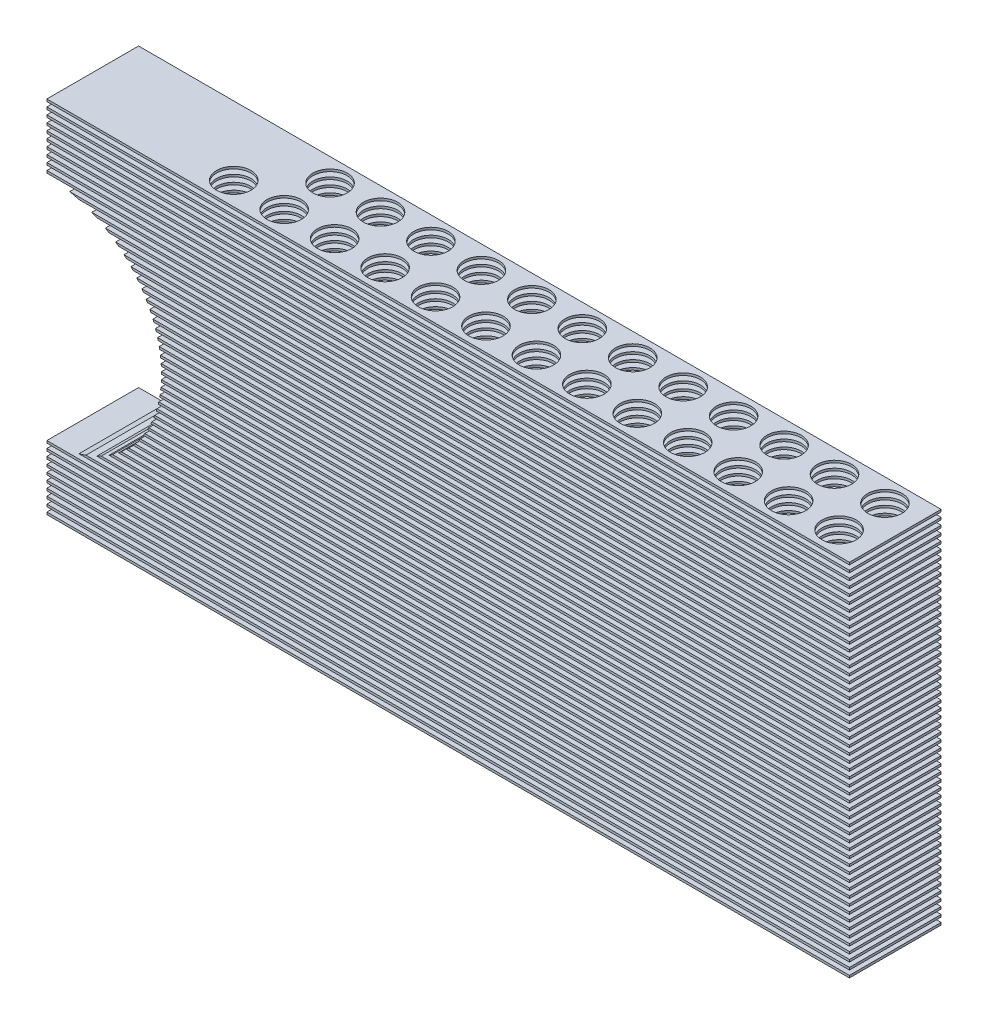
SolidWorks part; units mm, degrees
ref_plane "Alzado" through (0, 0, 0) normal (0, 0, 1) x (1, 0, 0)
ref_plane "Planta" through (0, 0, 0) normal (0, 1, 0) x (1, 0, 0)
ref_plane "Vista lateral" through (0, 0, 0) normal (1, 0, 0) x (0, 0, -1)
sketch "Croquis2" plane through (0, 0, 0) normal (0, 0, 1) x (1, 0, 0)
  line L0 (-175, 74) -> (-175, 75)
  line L2 (-175, 77) -> (-175, 78)
  line L4 (175, 77) -> (175, 78)
  line L5 (-175, 75) -> (175, 75)
  line L6 (175, 74) -> (-175, 74)
  line L7 (-175, 78) -> (175, 78)
  line L9 (175, 77) -> (-175, 77)
  line L11 (175, 74) -> (175, 75)
  line L12 (-175, 71) -> (-175, 72)
  line L13 (-175, 72) -> (175, 72)
  line L14 (175, 71) -> (-175, 71)
  line L15 (175, 71) -> (175, 72)
  line L16 (-175, 68) -> (-175, 69)
  line L17 (-175, 69) -> (175, 69)
  line L18 (175, 68) -> (-175, 68)
  line L19 (175, 68) -> (175, 69)
  line L20 (-175, 65) -> (-175, 66)
  line L21 (-175, 66) -> (175, 66)
  line L22 (175, 65) -> (-175, 65)
  line L23 (175, 65) -> (175, 66)
  line L24 (-175, 62) -> (-175, 63)
  line L25 (-175, 63) -> (175, 63)
  line L26 (175, 62) -> (-175, 62)
  line L27 (175, 62) -> (175, 63)
  line L28 (-175, 59) -> (-175, 60)
  line L29 (-175, 60) -> (175, 60)
  line L30 (175, 59) -> (-175, 59)
  line L31 (175, 59) -> (175, 60)
  line L32 (-175, 56) -> (-175, 57)
  line L33 (-175, 57) -> (175, 57)
  line L34 (175, 56) -> (-175, 56)
  line L35 (175, 56) -> (175, 57)
  line L36 (-175, 53) -> (-175, 54)
  line L37 (-175, 54) -> (175, 54)
  line L38 (175, 53) -> (-175, 53)
  line L39 (175, 53) -> (175, 54)
  line L40 (-175, 50) -> (-175, 51)
  line L41 (-175, 51) -> (175, 51)
  line L42 (175, 50) -> (-175, 50)
  line L43 (175, 50) -> (175, 51)
  line L45 (-165.0501, 48) -> (175, 48)
  line L46 (175, 47) -> (-161, 47)
  line L47 (175, 47) -> (175, 48)
  line L49 (-155.4041, 45) -> (175, 45)
  line L50 (175, 44) -> (-153.2055, 44)
  line L51 (175, 44) -> (175, 45)
  line L53 (-149.4853, 42) -> (175, 42)
  line L54 (175, 41) -> (-147.8707, 41)
  line L55 (175, 41) -> (175, 42)
  line L57 (-145, 39) -> (175, 39)
  line L58 (175, 38) -> (-143.711, 38)
  line L59 (175, 38) -> (175, 39)
  line L61 (-141.3697, 36) -> (175, 36)
  line L62 (175, 35) -> (-140.3013, 35)
  line L63 (175, 35) -> (175, 36)
  line L65 (-138.3394, 33) -> (175, 33)
  line L66 (175, 32) -> (-137.4367, 32)
  line L67 (175, 32) -> (175, 33)
  line L69 (-135.7699, 30) -> (175, 30)
  line L70 (175, 29) -> (-135, 29)
  line L71 (175, 29) -> (175, 30)
  line L73 (-133.5754, 27) -> (175, 27)
  line L74 (175, 26) -> (-132.9167, 26)
  line L75 (175, 26) -> (175, 27)
  line L77 (-131.6987, 24) -> (175, 24)
  line L78 (175, 23) -> (-131.1366, 23)
  line L79 (175, 23) -> (175, 24)
  line L81 (-130.1001, 21) -> (175, 21)
  line L82 (175, 20) -> (-129.6238, 20)
  line L83 (175, 20) -> (175, 21)
  line L85 (-128.7507, 18) -> (175, 18)
  line L86 (175, 17) -> (-128.3524, 17)
  line L87 (175, 17) -> (175, 18)
  line L89 (-127.6291, 15) -> (175, 15)
  line L90 (175, 14) -> (-127.303, 14)
  line L91 (175, 14) -> (175, 15)
  line L93 (-126.7196, 12) -> (175, 12)
  line L94 (175, 11) -> (-126.4614, 11)
  line L95 (175, 11) -> (175, 12)
  line L97 (-126.0102, 9) -> (175, 9)
  line L98 (175, 8) -> (-125.8167, 8)
  line L99 (175, 8) -> (175, 9)
  line L101 (-125.4924, 6) -> (175, 6)
  line L102 (175, 5) -> (-125.3613, 5)
  line L103 (175, 5) -> (175, 6)
  line L105 (-125.1603, 3) -> (175, 3)
  line L106 (175, 2) -> (-125.0901, 2)
  line L107 (175, 2) -> (175, 3)
  line L109 (-125.01, 0) -> (175, 0)
  line L110 (175, -1) -> (-125, -1)
  line L111 (175, -1) -> (175, 0)
  line L113 (-125.04, -3) -> (175, -3)
  line L114 (175, -4) -> (-125.0901, -4)
  line L115 (175, -4) -> (175, -3)
  line L117 (-125.2506, -6) -> (175, -6)
  line L118 (175, -7) -> (-125.3613, -7)
  line L119 (175, -7) -> (175, -6)
  line L121 (-125.6441, -9) -> (175, -9)
  line L122 (175, -10) -> (-125.8167, -10)
  line L123 (175, -10) -> (175, -9)
  line L125 (-126.225, -12) -> (175, -12)
  line L126 (175, -13) -> (-126.4614, -13)
  line L127 (175, -13) -> (175, -12)
  line L129 (-127, -15) -> (175, -15)
  line L130 (175, -16) -> (-127.303, -16)
  line L131 (175, -16) -> (175, -15)
  line L133 (-127.9787, -18) -> (175, -18)
  line L134 (175, -19) -> (-128.3524, -19)
  line L135 (175, -19) -> (175, -18)
  line L137 (-129.1742, -21) -> (175, -21)
  line L138 (175, -22) -> (-129.6238, -22)
  line L139 (175, -22) -> (175, -21)
  line L141 (-130.6041, -24) -> (175, -24)
  line L142 (175, -25) -> (-131.1366, -25)
  line L143 (175, -25) -> (175, -24)
  line L145 (-132.2917, -27) -> (175, -27)
  line L146 (175, -28) -> (-132.9167, -28)
  line L147 (175, -28) -> (175, -27)
  line L149 (-134.2692, -30) -> (175, -30)
  line L150 (175, -31) -> (-135, -31)
  line L151 (175, -31) -> (175, -30)
  line L153 (-136.5813, -33) -> (175, -33)
  line L154 (175, -34) -> (-137.4367, -34)
  line L155 (175, -34) -> (175, -33)
  line L157 (-139.2929, -36) -> (175, -36)
  line L158 (175, -37) -> (-140.3013, -37)
  line L159 (175, -37) -> (175, -36)
  line L161 (-142.5038, -39) -> (175, -39)
  line L162 (175, -40) -> (-143.711, -40)
  line L163 (175, -40) -> (175, -39)
  line L165 (-146.3818, -42) -> (175, -42)
  line L166 (175, -43) -> (-147.8707, -43)
  line L167 (175, -43) -> (175, -42)
  line L169 (-151.2513, -45) -> (175, -45)
  line L170 (175, -46) -> (-153.2055, -46)
  line L171 (175, -46) -> (175, -45)
  line L173 (-157.9413, -48) -> (175, -48)
  line L174 (175, -49) -> (-161, -49)
  line L175 (175, -49) -> (175, -48)
  line L176 (-175, -52) -> (-175, -51)
  line L177 (-175, -51) -> (175, -51)
  line L178 (175, -52) -> (-175, -52)
  line L179 (175, -52) -> (175, -51)
  line L180 (-175, -55) -> (-175, -54)
  line L181 (-175, -54) -> (175, -54)
  line L182 (175, -55) -> (-175, -55)
  line L183 (175, -55) -> (175, -54)
  line L184 (-175, -58) -> (-175, -57)
  line L185 (-175, -57) -> (175, -57)
  line L186 (175, -58) -> (-175, -58)
  line L187 (175, -58) -> (175, -57)
  line L188 (-175, -61) -> (-175, -60)
  line L189 (-175, -60) -> (175, -60)
  line L190 (175, -61) -> (-175, -61)
  line L191 (175, -61) -> (175, -60)
  line L192 (-175, -64) -> (-175, -63)
  line L193 (-175, -63) -> (175, -63)
  line L194 (175, -64) -> (-175, -64)
  line L195 (175, -64) -> (175, -63)
  line L196 (-175, -67) -> (-175, -66)
  line L197 (-175, -66) -> (175, -66)
  line L198 (175, -67) -> (-175, -67)
  line L199 (175, -67) -> (175, -66)
  line L200 (-175, -70) -> (-175, -69)
  line L201 (-175, -69) -> (175, -69)
  line L202 (175, -70) -> (-175, -70)
  line L203 (175, -70) -> (175, -69)
  line L204 (-175, -73) -> (-175, -72)
  line L205 (-175, -72) -> (175, -72)
  line L206 (175, -73) -> (-175, -73)
  line L207 (175, -73) -> (175, -72)
  line L208 (-175, -76) -> (-175, -75)
  line L209 (-175, -75) -> (175, -75)
  line L210 (175, -76) -> (-175, -76)
  line L211 (175, -76) -> (175, -75)
  line L212 (-175, -79) -> (-175, -78)
  line L213 (-175, -78) -> (175, -78)
  line L214 (175, -79) -> (-175, -79)
  line L215 (175, -79) -> (175, -78)
  line L221 (-175, 29) -> (-175, 30) [skipped]
  line L222 (-175, -43) -> (-175, -42) [skipped]
  line L223 (-175, 47) -> (-175, 48) [skipped]
  line L224 (-175, 44) -> (-175, 45) [skipped]
  line L225 (-175, 41) -> (-175, 42) [skipped]
  line L226 (-175, 38) -> (-175, 39) [skipped]
  line L227 (-175, 35) -> (-175, 36) [skipped]
  line L228 (-175, 32) -> (-175, 33) [skipped]
  line L229 (-175, 26) -> (-175, 27) [skipped]
  line L230 (-175, 23) -> (-175, 24) [skipped]
  line L231 (-175, 20) -> (-175, 21) [skipped]
  line L232 (-175, -19) -> (-175, -18) [skipped]
  line L233 (-175, -16) -> (-175, -15) [skipped]
  line L234 (-175, -13) -> (-175, -12) [skipped]
  line L235 (-175, -10) -> (-175, -9) [skipped]
  line L236 (-175, -7) -> (-175, -6) [skipped]
  line L237 (-175, -4) -> (-175, -3) [skipped]
  line L238 (-175, -1) -> (-175, 0) [skipped]
  line L239 (-175, 2) -> (-175, 3) [skipped]
  line L240 (-175, 17) -> (-175, 18) [skipped]
  line L241 (-175, 14) -> (-175, 15) [skipped]
  line L242 (-175, 11) -> (-175, 12) [skipped]
  line L243 (-175, 8) -> (-175, 9) [skipped]
  line L244 (-175, 5) -> (-175, 6) [skipped]
  line L245 (-175, -49) -> (-175, -48) [skipped]
  line L246 (-175, -46) -> (-175, -45) [skipped]
  line L247 (-175, -40) -> (-175, -39) [skipped]
  line L248 (-175, -22) -> (-175, -21) [skipped]
  line L249 (-175, -25) -> (-175, -24) [skipped]
  line L250 (-175, -28) -> (-175, -27) [skipped]
  line L251 (-175, -31) -> (-175, -30) [skipped]
  line L252 (-175, -34) -> (-175, -33) [skipped]
  line L253 (-175, -37) -> (-175, -36) [skipped]
  arc A0 (-161, -49) -> (-157.9413, -48) centre (-175, -1) ccw
  arc A1 (-153.2055, -46) -> (-151.2513, -45) centre (-175, -1) ccw
  arc A2 (-147.8707, -43) -> (-146.3818, -42) centre (-175, -1) ccw
  arc A3 (-143.711, -40) -> (-142.5038, -39) centre (-175, -1) ccw
  arc A4 (-140.3013, -37) -> (-139.2929, -36) centre (-175, -1) ccw
  arc A5 (-137.4367, -34) -> (-136.5813, -33) centre (-175, -1) ccw
  arc A6 (-128.3524, -19) -> (-127.9787, -18) centre (-175, -1) ccw
  arc A7 (-129.6238, -22) -> (-129.1742, -21) centre (-175, -1) ccw
  arc A8 (-131.1366, -25) -> (-130.6041, -24) centre (-175, -1) ccw
  arc A9 (-135, -31) -> (-134.2692, -30) centre (-175, -1) ccw
  arc A10 (-132.9167, -28) -> (-132.2917, -27) centre (-175, -1) ccw
  arc A11 (-127.303, -16) -> (-127, -15) centre (-175, -1) ccw
  arc A12 (-126.4614, -13) -> (-126.225, -12) centre (-175, -1) ccw
  arc A13 (-125.8167, -10) -> (-125.6441, -9) centre (-175, -1) ccw
  arc A14 (-125.3613, -7) -> (-125.2506, -6) centre (-175, -1) ccw
  arc A15 (-161, 47) -> (-165.0501, 48) centre (-175, -1) ccw
  arc A16 (-153.2055, 44) -> (-155.4041, 45) centre (-175, -1) ccw
  arc A17 (-147.8707, 41) -> (-149.4853, 42) centre (-175, -1) ccw
  arc A18 (-135, 29) -> (-135.7699, 30) centre (-175, -1) ccw
  arc A19 (-137.4367, 32) -> (-138.3394, 33) centre (-175, -1) ccw
  arc A20 (-140.3013, 35) -> (-141.3697, 36) centre (-175, -1) ccw
  arc A21 (-143.711, 38) -> (-145, 39) centre (-175, -1) ccw
  arc A22 (-132.9167, 26) -> (-133.5754, 27) centre (-175, -1) ccw
  arc A23 (-131.1366, 23) -> (-131.6987, 24) centre (-175, -1) ccw
  arc A24 (-129.6238, 20) -> (-130.1001, 21) centre (-175, -1) ccw
  arc A25 (-128.3524, 17) -> (-128.7507, 18) centre (-175, -1) ccw
  arc A26 (-127.303, 14) -> (-127.6291, 15) centre (-175, -1) ccw
  arc A27 (-126.4614, 11) -> (-126.7196, 12) centre (-175, -1) ccw
  arc A28 (-125.8167, 8) -> (-126.0102, 9) centre (-175, -1) ccw
  arc A29 (-125.3613, 5) -> (-125.4924, 6) centre (-175, -1) ccw
  arc A30 (-125.0901, 2) -> (-125.1603, 3) centre (-175, -1) ccw
  arc A31 (-125, -1) -> (-125.01, 0) centre (-175, -1) ccw
  arc A32 (-125.0901, -4) -> (-125.04, -3) centre (-175, -1) ccw
  point P0 (0, 0)
  dimension "D1" = 53
extrude "Saliente-Extruir2" add sketch "Croquis2" along normal blind 40
sketch "Croquis3" plane through (0, 78, 0) normal (0, 1, 0) x (1, 0, 0)
  circle A152 centre (160.5, -10) radius 7.5
  circle A153 centre (138.5, -10) radius 7.5
  circle A154 centre (116.5, -10) radius 7.5
  circle A155 centre (94.5, -10) radius 7.5
  circle A156 centre (72.5, -10) radius 7.5
  circle A157 centre (50.5, -10) radius 7.5
  circle A158 centre (28.5, -10) radius 7.5
  circle A159 centre (6.5, -10) radius 7.5
  circle A160 centre (-15.5, -10) radius 7.5
  circle A161 centre (-37.5, -10) radius 7.5
  circle A162 centre (-59.5, -10) radius 7.5
  circle A163 centre (-81.5, -10) radius 7.5
  circle A169 centre (138.5, -30) radius 7.5
  circle A170 centre (116.5, -30) radius 7.5
  circle A171 centre (94.5, -30) radius 7.5
  circle A172 centre (72.5, -30) radius 7.5
  circle A173 centre (50.5, -30) radius 7.5
  circle A174 centre (28.5, -30) radius 7.5
  circle A175 centre (6.5, -30) radius 7.5
  circle A176 centre (-15.5, -30) radius 7.5
  circle A177 centre (-37.5, -30) radius 7.5
  circle A178 centre (-59.5, -30) radius 7.5
  circle A179 centre (-81.5, -30) radius 7.5
  circle A180 centre (-103.5, -30) radius 7.5
  circle A181 centre (160.5, -30) radius 7.5
  circle A182 centre (-103.5, -10) radius 7.5 [skipped]
extrude "Cortar-Extruir1" cut sketch "Croquis3" against normal blind 180
